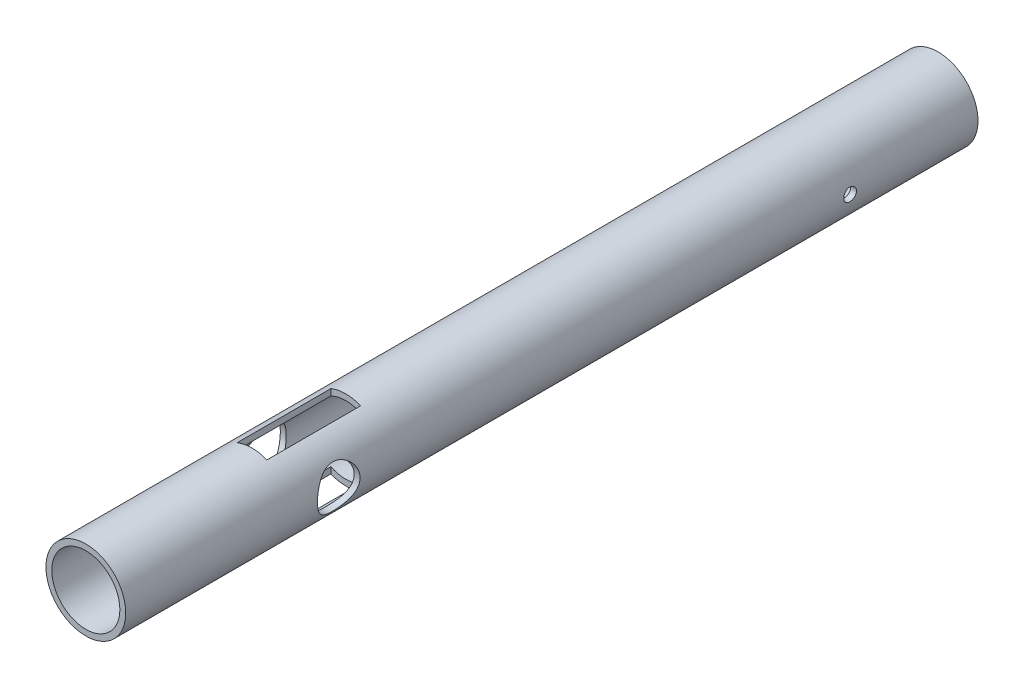
SolidWorks part; units mm, degrees
material "6061-T4 (SS)"
ref_plane "Front" through (0, 0, 0) normal (0, 0, 1) x (1, 0, 0)
ref_plane "Top" through (0, 0, 0) normal (0, 1, 0) x (1, 0, 0)
ref_plane "Right" through (0, 0, 0) normal (1, 0, 0) x (0, 0, -1)
sketch "Sketch1" plane through (0, 0, 0) normal (0, 0, 1) x (1, 0, 0)
  circle A0 centre (0, 0) radius 9.36
  circle A1 centre (0, 0) radius 7.99
extrude "Extrude1" add sketch "Sketch1" along normal blind 200
sketch "Sketch2" plane through (0, 0, 0) normal (1, 0, 0) x (0, 0, -1)
  line L0 (-30, -47.5362) -> (-30, 39.1475) construction
  line L1 (0, -9.36) -> (0, 9.36) construction
  line L2 (-150, -93.5027) -> (-150, 51.4365) construction
  circle A0 centre (-30, 0) radius 1.5
  circle A1 centre (-150, 0) radius 5
  dimension "D2" = 150
  dimension "D1" = 30
extrude "Extrude2" cut sketch "Sketch2" against normal through all and the other way through all
sketch "Sketch3" plane through (0, 0, 0) normal (0, 1, 0) x (1, 0, 0)
  line L0 (-54.8402, -150) -> (72.4613, -150) construction
  line L1 (7.99, 0) -> (-7.99, 0) construction
  line L2 (-44.3384, -139) -> (38.4408, -139) construction
  line L3 (-76.6388, -161) -> (67.6466, -161) construction
  line L4 (3.5, -160.8387) -> (3.5, -87.3966) construction
  line L5 (0, -179.9469) -> (0, -88.7091) construction
  line L6 (-3.5, -169.4108) -> (-3.5, -98.3485) construction
  line L8 (-3.5, -139) -> (3.5, -139)
  line L9 (-3.5, -139) -> (-3.5, -161)
  line L10 (-3.5, -161) -> (3.5, -161)
  line L11 (3.5, -139) -> (3.5, -161)
  dimension "D1" = 150
  dimension "D2" = 11
  dimension "D3" = 22
  dimension "D4" = 3.5
  dimension "D5" = 7
extrude "Extrude3" cut sketch "Sketch3" against normal blind 25 and the other way blind 25
